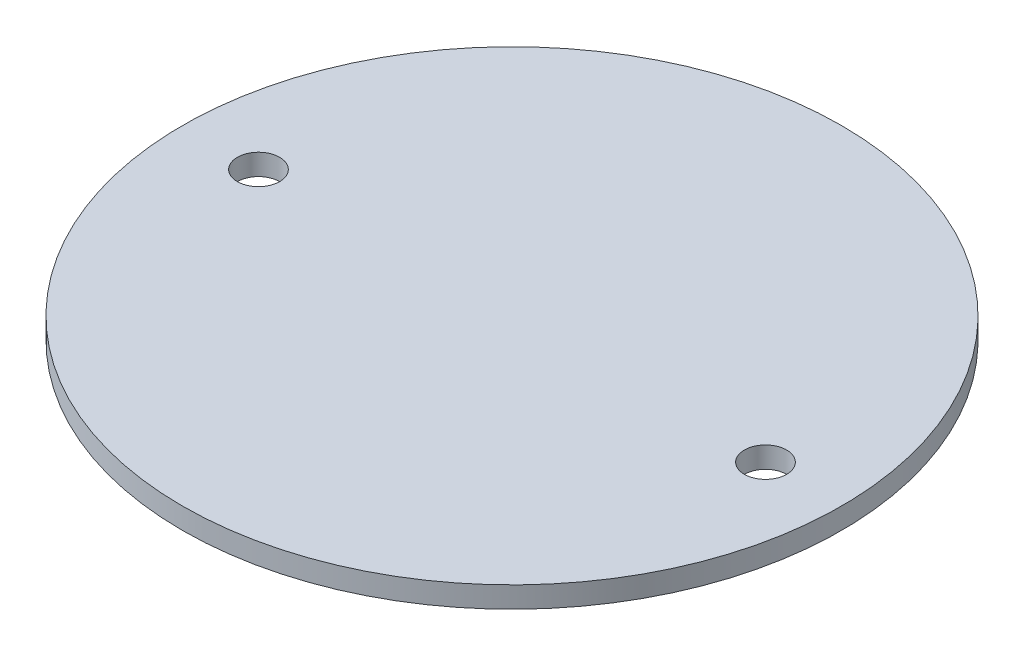
SolidWorks part; units mm, degrees
ref_plane "Front Plane" through (0, 0, 0) normal (0, 0, 1) x (1, 0, 0)
ref_plane "Top Plane" through (0, 0, 0) normal (0, 1, 0) x (1, 0, 0)
ref_plane "Right Plane" through (0, 0, 0) normal (1, 0, 0) x (0, 0, -1)
sketch "Sketch1" plane through (0, 0, 0) normal (0, 1, 0) x (1, 0, 0)
  circle A0 centre (0, 0) radius 49.53
  dimension "D1" = 99.06
extrude "Boss-Extrude1" add sketch "Sketch1" along normal blind 3.175
extrude "Cut-Extrude1" cut sketch "Sketch2" against normal blind 263.398
sketch "Sketch2" plane through (-55.0397, 234.95, -116.0884) normal (0, 1, 0) x (-1, 0, 0)
  circle A0 centre (-93.1397, 116.0884) radius 3.175
  circle A1 centre (-16.9397, 116.0884) radius 3.175
  point P4 (0, 0)
  point P6 (0, 0)
